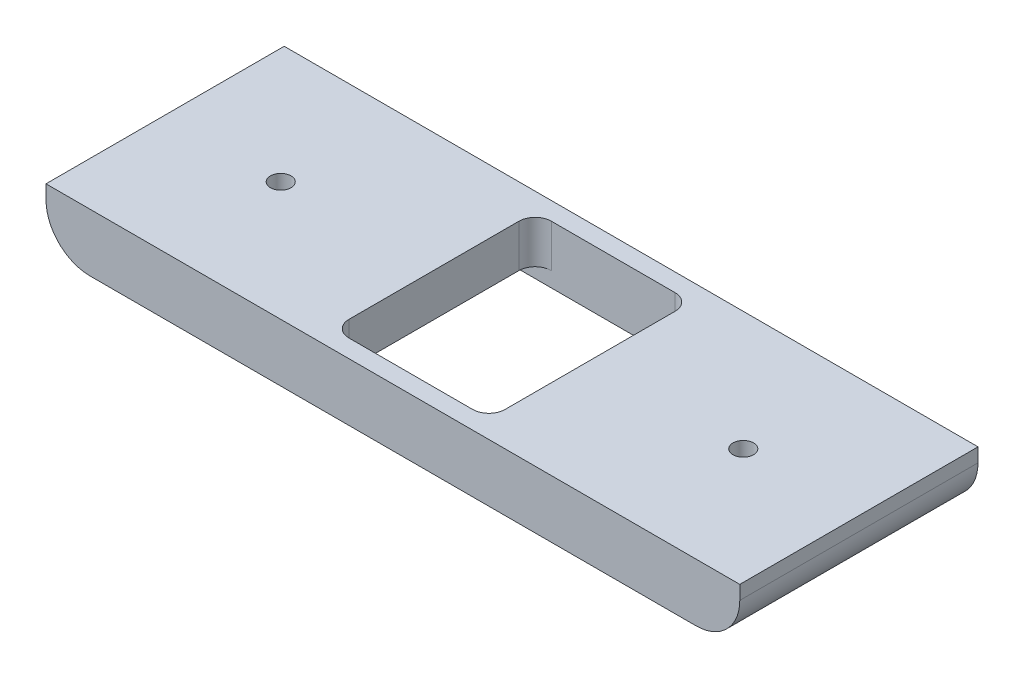
SolidWorks part; units mm, degrees
material "1060 Alloy"
ref_plane "Front Plane" through (0, 0, 0) normal (0, 0, 1) x (1, 0, 0)
ref_plane "Top Plane" through (0, 0, 0) normal (0, 1, 0) x (1, 0, 0)
ref_plane "Right Plane" through (0, 0, 0) normal (1, 0, 0) x (0, 0, -1)
sketch "Sketch1" plane through (0, 0, 0) normal (0, 1, 0) x (1, 0, 0)
  line L0 (-38.1, -13.081) -> (38.1, 13.081) construction
  line L1 (-38.1, 13.081) -> (38.1, 13.081)
  line L2 (-38.1, 13.081) -> (-38.1, -13.081)
  line L3 (-38.1, -13.081) -> (38.1, -13.081)
  line L4 (38.1, 13.081) -> (38.1, -13.081)
  line L5 (-38.1, 13.081) -> (38.1, -13.081) construction
  line L11 (38.1, -26.67) -> (38.1, -11.1125) construction
  line L12 (-38.1, -11.1125) -> (-38.1, -26.67) construction
  point P0 (0, 0)
  point P10 (0, 0)
  dimension "D1" = 26.162
extrude "Boss-Extrude1" add sketch "Sketch1" along normal blind 6.35
fillet "Fillet1" radius 4.826 2 edges at (38.1, 0, 0) (-38.1, 0, 0)
sketch "Sketch2" plane through (38.1, 0, 0) normal (1, 0, 0) x (0, 0, -1)
  line L0 (-11.1125, 0) -> (-11.1125, 1.651)
  line L1 (-13.081, 0) -> (13.081, 0) construction
  line L2 (-11.1125, 1.651) -> (11.1125, 1.651)
  line L3 (11.1125, 1.651) -> (11.1125, 0)
  line L7 (-11.1125, 0) -> (11.1125, 0)
  line L8 (-11.1125, -1.851) -> (-11.1125, -0.2) construction
  line L9 (11.1125, -1.851) -> (11.1125, -0.2) construction
extrude "Cut-Extrude1" cut sketch "Sketch2" against normal through all
sketch "Sketch3" plane through (0, 1.651, 0) normal (0, -1, 0) x (1, 0, 0)
  line L0 (6.7945, -11.1125) -> (-6.7945, -11.1125) construction
  line L1 (8.5725, 9.3345) -> (8.5725, -9.3345) construction
  line L2 (-6.7945, 11.1125) -> (6.7945, 11.1125) construction
  line L3 (-8.5725, -9.3345) -> (-8.5725, 9.3345) construction
  line L4 (6.7945, -11.1125) -> (-6.7945, -11.1125)
  line L5 (8.5725, 9.3345) -> (8.5725, -9.3345)
  line L6 (-6.7945, 11.1125) -> (6.7945, 11.1125)
  line L7 (-8.5725, -9.3345) -> (-8.5725, 9.3345)
  arc A0 (6.7945, -11.1125) -> (8.5725, -9.3345) centre (6.7945, -9.3345) ccw construction
  arc A1 (8.5725, 9.3345) -> (6.7945, 11.1125) centre (6.7945, 9.3345) ccw construction
  arc A2 (-6.7945, 11.1125) -> (-8.5725, 9.3345) centre (-6.7945, 9.3345) ccw construction
  arc A3 (-8.5725, -9.3345) -> (-6.7945, -11.1125) centre (-6.7945, -9.3345) ccw construction
  arc A4 (6.7945, -11.1125) -> (8.5725, -9.3345) centre (6.7945, -9.3345) ccw
  arc A5 (8.5725, 9.3345) -> (6.7945, 11.1125) centre (6.7945, 9.3345) ccw
  arc A6 (-6.7945, 11.1125) -> (-8.5725, 9.3345) centre (-6.7945, 9.3345) ccw
  arc A7 (-8.5725, -9.3345) -> (-6.7945, -11.1125) centre (-6.7945, -9.3345) ccw
extrude "Cut-Extrude2" cut sketch "Sketch3" against normal through all and the other way through all
hole_wizard "#4-40 Tapped Hole1" positions "Sketch6" profile "Sketch7" tap size "#4-40" standard "Ansi Inch" end condition through all
sketch "Sketch6" plane through (0, 6.35, 0) normal (0, 1, 0) x (-1, 0, 0)
  point P1 (25.4, 0)
  point P4 (-25.4, 0)
sketch "Sketch7" plane through (-25.4, 6.35, 0) normal (1, 0, 0) x (0, 0, 1)
  line L0 (0, 0) -> (0, 6.35)
  line L1 (0, 6.35) -> (1.1303, 6.35)
  line L2 (1.1303, 6.35) -> (1.1303, 0)
  line L5 (1.1303, 0) -> (0, 0)
  line L11 (0, -6.35) -> (0, 107.95) construction
  dimension "Thru Tap Drill Dia." = 2.2606
  dimension "Thru Tap Drill Depth" = 6.35
cosmetic thread "Hole Thread1" parameters "D2"=2.8448
cosmetic thread "Hole Thread2" parameters "D2"=2.8448
